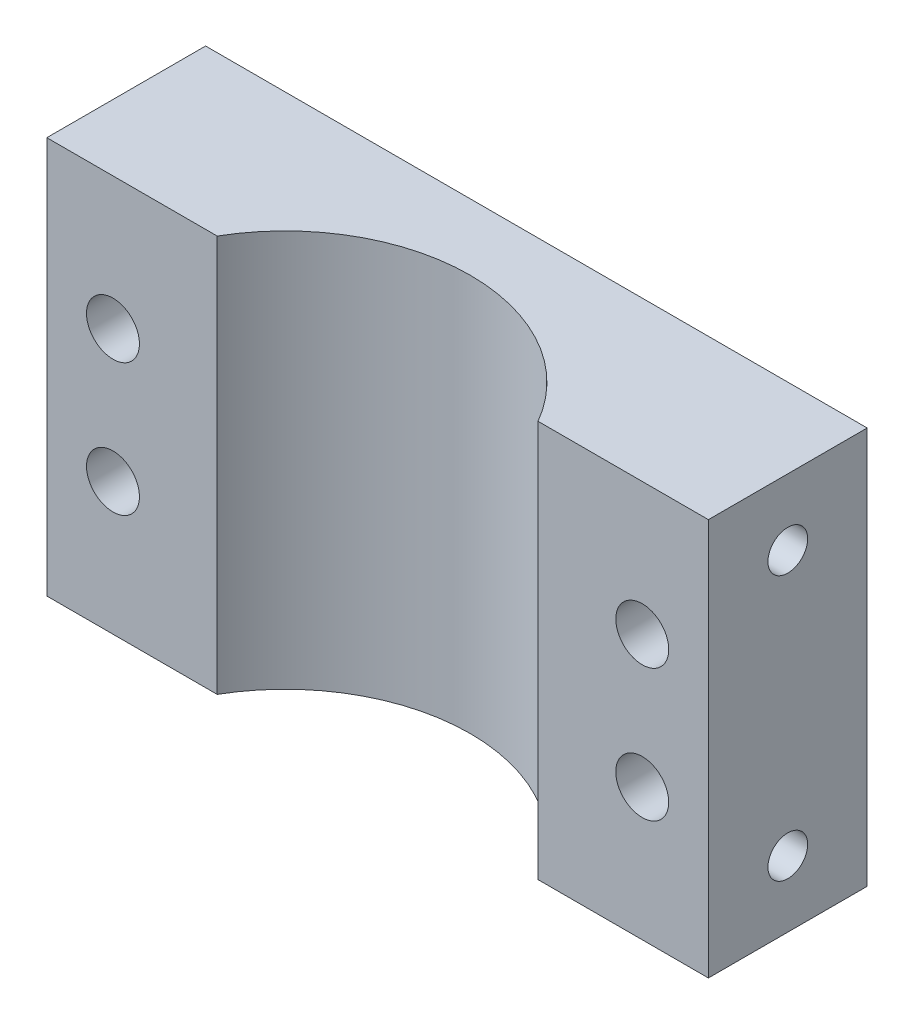
SolidWorks part; units mm, degrees
ref_plane "Plan de face" through (0, 0, 0) normal (0, 0, 1) x (1, 0, 0)
ref_plane "Plan de dessus" through (0, 0, 0) normal (0, 1, 0) x (1, 0, 0)
ref_plane "Plan de droite" through (0, 0, 0) normal (1, 0, 0) x (0, 0, -1)
sketch "Esquisse1" plane through (0, 0, 0) normal (0, 1, 0) x (1, 0, 0)
  line L0 (0, 0) -> (0, 19.04) construction
  line L1 (0, 0) -> (-12.1244, 7) construction
  line L2 (0, 0) -> (12.1244, 7) construction
  line L3 (-12.1244, 7) -> (-12.1244, 19)
  line L4 (-12.1244, 19) -> (12.1244, 19)
  line L5 (12.1244, 19) -> (12.1244, 7)
  line L6 (-18.3481, 0) -> (19.8422, 0) construction
  line L7 (-12.1244, 7) -> (12.1244, 7) construction
  line L8 (0, 14) -> (12.1244, 14) construction
  line L9 (-12.1244, 19) -> (-25, 19)
  line L10 (0, 14) -> (-12.1244, 14) construction
  line L11 (-12.1244, 7) -> (-25, 7)
  line L12 (-25, 19) -> (-25, 7)
  line L13 (12.1244, 19) -> (25, 19)
  line L15 (12.1244, 7) -> (25, 7)
  line L16 (25, 19) -> (25, 7)
  arc A0 (-12.1244, 7) -> (12.1244, 7) centre (0, 0) cw
  dimension "D1" = 14
  dimension "D2" = 5
  dimension "D3" = 7
  dimension "D4" = 50
extrude "Boss.-Extru.3" add sketch "Esquisse1" along normal blind 30 contours L3 A0 L5 L4 region at (0, 0, -15.2084)
extrude "Boss.-Extru.4" add sketch "Esquisse1<5>" along normal blind 30 contours L9 L12 L11 L3 | L16 L13 L5 L15 region at (-18.5622, 0, -13) region at (18.5622, 0, -13)
sketch "Esquisse1<5>" plane through (0, 0, 0) normal (0, 1, 0) x (1, 0, 0) same geometry as "Esquisse1"
sketch "Esquisse9" plane through (-25, 0, 0) normal (-1, 0, 0) x (0, 0, 1)
  line L0 (-13, 0) -> (-13, 5) construction
  line L1 (-19, 0) -> (-7, 0) construction
  line L2 (-13, 5) -> (-13, 25) construction
  line L3 (-13, 25) -> (-13, 30) construction
  line L4 (-19, 30) -> (-7, 30) construction
  line L5 (-13, 25) -> (-19, 25) construction
  line L6 (-19, 30) -> (-19, 0) construction
  line L7 (-13, 25) -> (-7, 25) construction
  line L8 (-7, 30) -> (-7, 0) construction
  circle A0 centre (-13, 25) radius 1.5
  circle A1 centre (-13, 5) radius 1.5
  dimension "D3" = 3
  dimension "D1" = 20
  dimension "D2" = 5
sketch "Esquisse10" plane through (25, 0, 0) normal (1, 0, 0) x (0, 0, -1)
  circle A0 centre (13, 25) radius 1.5
  circle A1 centre (13, 5) radius 1.5
  circle A2 centre (13, 5) radius 1.5 construction
  circle A3 centre (13, 25) radius 1.5 construction
extrude "Enlèv. mat.-Extru.1" cut sketch "Esquisse10" against normal blind 3
extrude "Enlèv. mat.-Extru.2" cut sketch "Esquisse9" against normal blind 3 contours A0 | A1
sketch "Esquisse11" plane through (0, 0, -19) normal (0, 0, -1) x (-1, 0, 0)
  line L0 (-25, 20) -> (-20, 20) construction
  line L1 (-25, 30) -> (-25, 0) construction
  line L2 (-20, 20) -> (20, 20) construction
  line L3 (20, 20) -> (25, 20) construction
  line L4 (25, 30) -> (25, 0) construction
  line L5 (-20, 30) -> (-20, 20) construction
  line L6 (25, 30) -> (-25, 30) construction
  line L7 (-20, 20) -> (-20, 10) construction
  line L8 (-20, 10) -> (-25, 10) construction
  line L9 (-20, 0) -> (-20, 10) construction
  line L10 (25, 0) -> (-25, 0) construction
  line L11 (-20, 10) -> (20, 10) construction
  line L12 (20, 10) -> (20, 0) construction
  line L13 (25, 10) -> (20, 10) construction
  line L14 (20, 10) -> (20, 20) construction
  line L15 (20, 20) -> (20, 30) construction
  circle A0 centre (-20, 20) radius 2
  circle A1 centre (20, 20) radius 2
  circle A2 centre (-20, 10) radius 2
  circle A3 centre (20, 10) radius 2
  dimension "D4" = 4
  dimension "D1" = 5
  dimension "D2" = 10
  dimension "D3" = 10
extrude "Enlèv. mat.-Extru.3" cut sketch "Esquisse11" against normal through all contours A2 | A3 | A1 | A0
